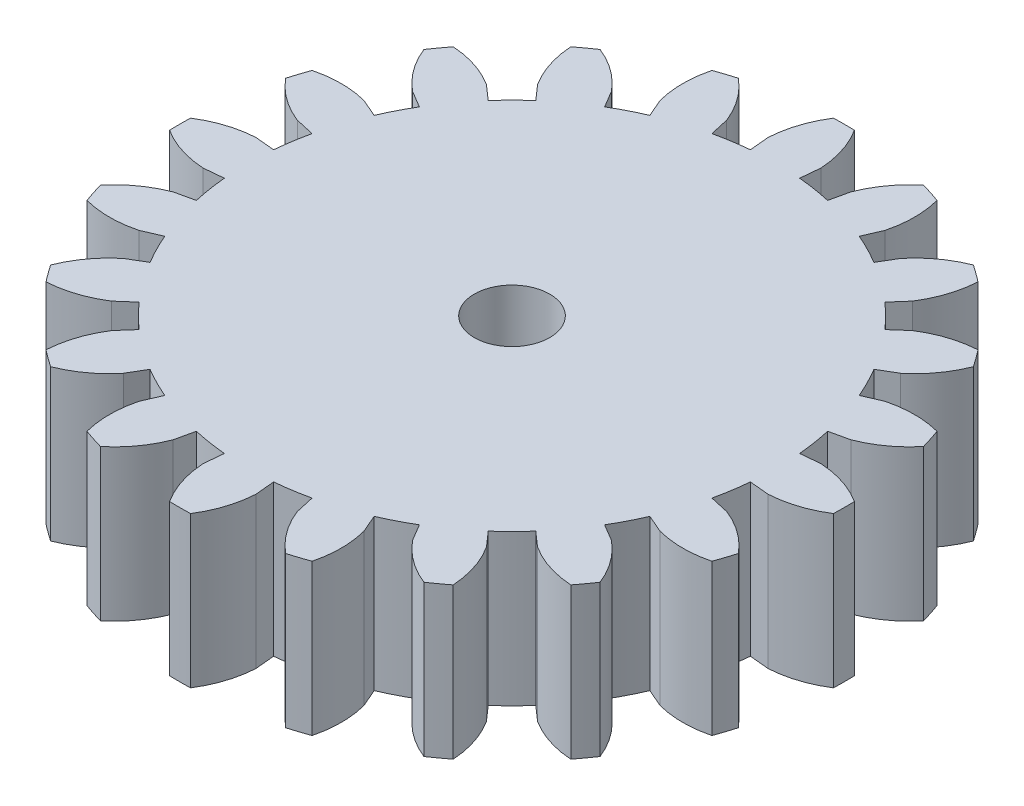
SolidWorks part; units mm, degrees
ref_plane "Спереди" through (0, 0, 0) normal (0, 0, 1) x (1, 0, 0)
ref_plane "Сверху" through (0, 0, 0) normal (0, 1, 0) x (1, 0, 0)
ref_plane "Справа" through (0, 0, 0) normal (1, 0, 0) x (0, 0, -1)
other "Configuration Table"
sketch "Эскиз1" plane through (0, 0, 0) normal (0, 1, 0) x (1, 0, 0)
  circle A0 centre (0, 0) radius 17.5
  dimension "D1" = 35
extrude "Бобышка-Вытянуть1" add sketch "Эскиз1" along normal blind 10
sketch "Эскиз2" plane through (0, 0, 0) normal (0, -1, 0) x (1, 0, 0)
  line L0 (0, 0) -> (0, 22) construction
  line L1 (0, 0) -> (-1.7523, 18.712) construction
  line L2 (0, 0) -> (1.7523, 18.712) construction
  line L5 (-1.5692, 19.9383) -> (0, 0) construction
  line L6 (0, 0) -> (1.5692, 19.9383) construction
  line L7 (-0.6949, 21.989) -> (0, 0) construction
  line L8 (-1.6317, 17.4238) -> (-1.7523, 18.712)
  line L9 (1.7523, 18.712) -> (1.6317, 17.4238)
  circle A0 centre (0, 0) radius 18.7938 construction
  circle A1 centre (0, 0) radius 20 construction
  circle A2 centre (0, 0) radius 22 construction
  arc A3 (-0.6949, 21.989) -> (0.6949, 21.989) centre (0, 0) cw
  arc A4 (-1.6317, 17.4238) -> (1.6317, 17.4238) centre (0, 0) cw
  circle A5 centre (0, 0) radius 17.5 construction
  arc A6 (-1.5692, 19.9383) -> (1.5692, 19.9383) centre (0, 0) cw construction
  arc A7 (-1.7523, 18.712) -> (-0.6949, 21.989) centre (5.0681, 18.3203) cw
  arc A8 (0.6949, 21.989) -> (1.7523, 18.712) centre (-5.0681, 18.3203) cw
  point P12 (0, 20)
  point P16 (0, 22)
  point P22 (0, 17.5)
  dimension "D1" = 37.5877
  dimension "D2" = 40
  dimension "D3" = 44
  dimension "D4" = 5.35
  dimension "D5" = 4.5
  dimension "D6" = 1.81
extrude "Бобышка-Вытянуть2" add sketch "Эскиз2" against normal blind 10
pattern_circular "Круговой массив1" count 20 over 360 about axis through (0, 10, 0) along (0, -1, 0) of "Бобышка-Вытянуть2" reverse direction yes
sketch "Эскиз3" plane through (0, 0, 0) normal (0, -1, 0) x (1, 0, 0)
  circle A0 centre (0, 0) radius 2.5
  dimension "D1" = 5
extrude "Вырез-Вытянуть1" cut sketch "Эскиз3" against normal through all
equation "\"Ширина груза\"= 420"
equation "\"Глубина груза\"= 490"
equation "\"Высота груза\"= 297"
equation "\"Ширина ячейки\"= \"Ширина груза\" + 10"
equation "\"Глубина ячейки\"= \"Глубина груза\" + 10"
equation "\"Высота ячейки\"= \"Высота груза\" + 10 + 13"
equation "\"Колво ячеек ширина\"= 2"
equation "\"Колво ячеек высота\"= 2"
equation "\"Толщина стенки\" = 6"
equation "\"Крепление дверцы\"= 5 "
equation "\"Ширина рейки\"= \"Толщина шестерни\""
equation "\"Высота рейки\"= 20"
equation "\"Высота пола\"= \"Толщина стенки\" * 2"
equation "\"Колво полозьев\"= 5"
equation "\"Отступ рейки\"= 20"
equation "\"Глубина каретки\"= \"Глубина ячейки\" + 30 + \"Мотор Y высота корпуса\" + 20"
equation "\"Длинна рейки\" = (\"Ширина ячейки\" + \"Толщина стенки\" + \"Крепление дверцы\") * \"Колво ячеек ширина\" + \"Ширина ячейки выгрузки\" * \"Колво выгрузки\" + \"Толщина стенки\" + \"Отступ крепления мотора фиксации\" * 2 - \"Крепление дверцы\" * \"Колво ячеек ширина\""
equation "\"Отступ шпильки\"= 26"
equation "\"Диаметр шпильки\"= 5"
equation "\"Длинна шпильки\"= ( \"Высота ячейки\" + \"Толщина стенки\" + \"Высота пола\" ) * \"Колво ячеек высота\" + ( \"Толщина стенки\" + \"Отступ рейки\" ) * 2 "
equation "\"Ширина пластины\"= 50  "
equation "\"Высота зона выгрузки\"= \"Высота ячейки\" * 2 + \"Толщина стенки\" * 2"
equation "\"Колво выгрузки\"= 1"
equation "\"Ширина ячейки выгрузки\"= \"Ширина ячейки\" + \"Толщина стенки\" + \"Отступ крепления мотора фиксации\"*2"
equation "\"Отступ крепления мотора фиксации\" = (\"Ширина пластины\" + 20 - \"Толщина стенки\") / 2"
equation "\"Мотор X ширина корпуса\"= 42.3"
equation "\"Мотор X высота корпуса\"= 42.3"
equation "\"Мотор X длина корпуса\"= 40"
equation "\"Мотор X вылет вала\"= 19.8"
equation "\"Мотор Y ширина корпуса\"= 42.3"
equation "\"Мотор Y высота корпуса\"= 42.3"
equation "\"Мотор Y длина корпуса\"= 48"
equation "\"Мотор Y вылет вала\"= 30"
equation "\"Мотор Z ширина корпуса\"= 42"
equation "\"Мотор Z высота корпуса\"= 42"
equation "\"Мотор Z длина корпуса\"= 40"
equation "\"Мотор Z вылет вала\"= 23"
equation "\"Мотор диаметр вала ПРЕДВ\"= 5"
equation "\"Мотор шаг крепления ПРЕДВ\"= 31"
equation "\"Мотор диаметр отверстий ПРЕДВ\"= 3"
equation "\"Мотор глубина отверстий ПРЕДВ\"= 4.5"
equation "\"Мотор диаметр буртика ПРЕДВ\"= 22"
equation "\"Мотор высота буртика ПРЕДВ\"= 2"
equation "\"Мотор диаметр шкива ПРЕДВ\"= 16"
equation "\"Мотор длина шкива ПРЕДВ\"= 12"
equation "\"Мотор отступ шкива ПРЕДВ\"= 5"
equation "\"Мотор X шаг градусов\"= 1.8"
equation "\"Мотор Y шаг градусов\"= 1.8"
equation "\"Мотор Z шаг градусов\"= 1.8"
equation "\"Мотор Y диаметр ротора\"= 25.78"
equation "\"Толщина шестерни\"= 10"
equation "\"D1@Бобышка-Вытянуть1\"=\"Толщина шестерни\""
equation "\"D1@Бобышка-Вытянуть2\"=\"Толщина шестерни\""
equation "\"D1@Эскиз3\"=\"Мотор диаметр вала ПРЕДВ\""
